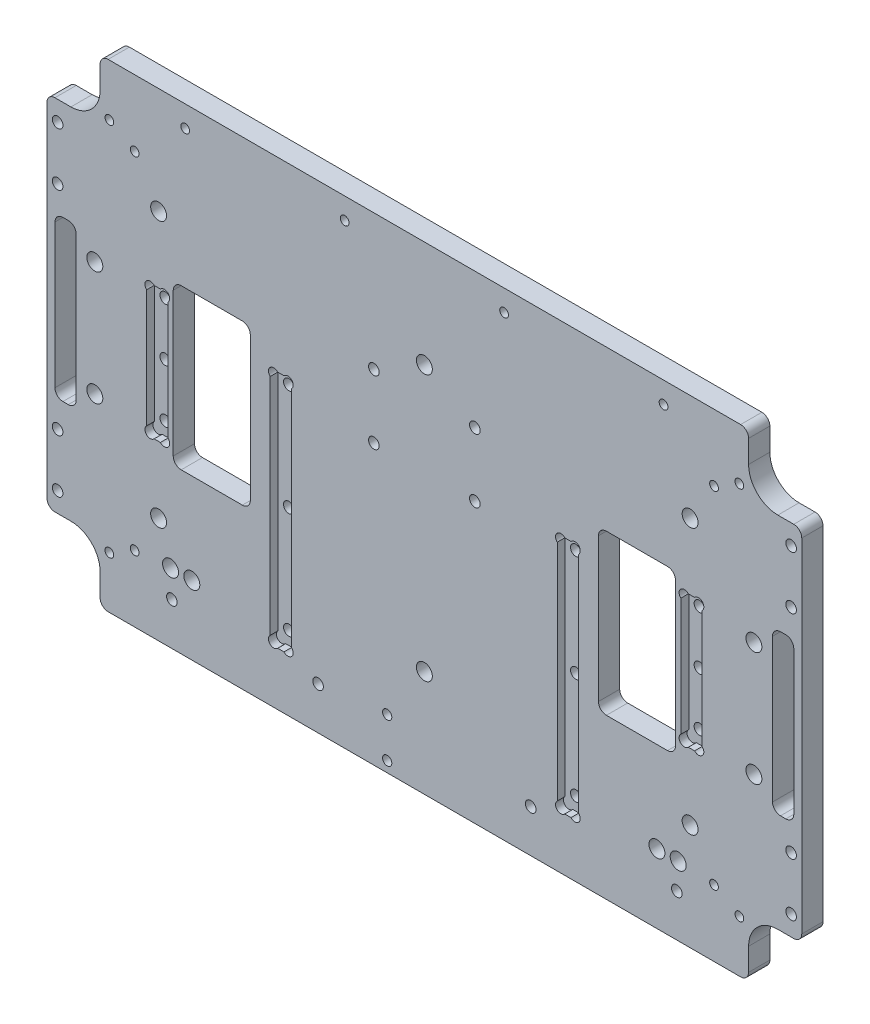
SolidWorks part; units mm, degrees
ref_plane "Front" through (0, 0, 0) normal (0, 0, 1) x (1, 0, 0)
ref_plane "Top" through (0, 0, 0) normal (0, 1, 0) x (1, 0, 0)
ref_plane "Right" through (0, 0, 0) normal (1, 0, 0) x (0, 0, -1)
sketch "Esquisse1" plane through (0, 0, 0) normal (0, 0, 1) x (1, 0, 0)
  line L1 (0, 0) -> (284, 0)
  line L2 (0, 0) -> (0, 180)
  line L3 (0, 180) -> (284, 180)
  line L4 (284, 0) -> (284, 180)
  dimension "D1" = 284
  dimension "D2" = 180
extrude "Boss.-Extru.1" add sketch "Esquisse1" along normal blind 8
sketch "Esquisse2" plane through (0, 0, 8) normal (0, 0, 1) x (1, 0, 0)
  line L0 (142, 180) -> (142, 0) construction
  line L1 (47.5, 60) -> (76.5, 60)
  line L2 (47.5, 60) -> (47.5, 120)
  line L3 (47.5, 120) -> (76.5, 120)
  line L4 (76.5, 60) -> (76.5, 120)
  line L5 (284, 180) -> (0, 180) construction
  line L6 (0, 0) -> (284, 0) construction
  line L7 (76.5, 90) -> (142, 90) construction
  line L8 (62, 60) -> (62, 120) construction
  line L9 (47.5, 90) -> (11, 90) construction
  line L10 (7, 60) -> (7, 120) construction
  line L11 (3, 60) -> (11, 60)
  line L12 (3, 60) -> (3, 120)
  line L13 (3, 120) -> (11, 120)
  line L14 (11, 60) -> (11, 120)
  line L15 (277, 60) -> (277, 120) construction
  line L16 (236.5, 90) -> (273, 90) construction
  line L17 (222, 60) -> (222, 120) construction
  line L18 (273, 60) -> (273, 120)
  line L19 (281, 120) -> (273, 120)
  line L20 (281, 60) -> (281, 120)
  line L21 (281, 60) -> (273, 60)
  line L22 (207.5, 60) -> (207.5, 120)
  line L23 (236.5, 120) -> (207.5, 120)
  line L24 (236.5, 60) -> (236.5, 120)
  line L25 (236.5, 60) -> (207.5, 60)
  dimension "D1" = 90
  dimension "D2" = 60
  dimension "D3" = 29
  dimension "D4" = 160
  dimension "D5" = 8
  dimension "D6" = 60
  dimension "D7" = 270
extrude "Enlèv. mat.-Extru.1" cut sketch "Esquisse2" against normal through all
sketch "Esquisse3" plane through (0, 0, 8) normal (0, 0, 1) x (1, 0, 0)
  line L0 (0, 172) -> (284, 172) construction
  line L1 (0, 180) -> (0, 0) construction
  line L2 (284, 0) -> (284, 180) construction
  line L3 (112, 172) -> (112, 180.3897) construction
  line L5 (172, 172) -> (172, 180.3897) construction
  line L6 (172, 180.3897) -> (112, 180.3897) construction
  line L7 (142, 180.3897) -> (142, 180) construction
  line L8 (284, 180) -> (0, 180) construction
  circle A0 centre (112, 172) radius 1.65
  circle A1 centre (172, 172) radius 1.65
  circle A2 centre (232, 172) radius 1.65
  circle A4 centre (52, 172) radius 1.65
  dimension "D1" = 3.3
  dimension "D2" = 4
  dimension "D3" = 8
  dimension "D4" = 60
extrude "Enlèv. mat.-Extru.2" cut sketch "Esquisse3" against normal up to vertex (8 mm away) up to point (284, 180, 0)
sketch "Esquisse4" plane through (0, 0, 8) normal (0, 0, 1) x (1, 0, 0)
  line L0 (142, 0) -> (142, 180) construction
  line L1 (84, 110) -> (92, 110)
  line L2 (84, 110) -> (84, 20)
  line L3 (84, 20) -> (92, 20)
  line L4 (92, 110) -> (92, 20)
  line L5 (0, 0) -> (284, 0) construction
  line L6 (284, 180) -> (0, 180) construction
  line L8 (76.5, 60) -> (76.5, 120) construction
  line L9 (192, 110) -> (192, 20)
  line L10 (200, 20) -> (192, 20)
  line L11 (200, 110) -> (200, 20)
  line L12 (200, 110) -> (192, 110)
  line L13 (47.5, 120) -> (47.5, 60) construction
  line L14 (37.5, 115) -> (45.5, 115)
  line L15 (37.5, 115) -> (37.5, 65)
  line L16 (37.5, 65) -> (45.5, 65)
  line L17 (45.5, 115) -> (45.5, 65)
  line L18 (45.5, 90) -> (47.5, 90) construction
  line L19 (238.5, 90) -> (236.5, 90) construction
  line L20 (238.5, 115) -> (238.5, 65)
  line L21 (246.5, 65) -> (238.5, 65)
  line L22 (246.5, 115) -> (246.5, 65)
  line L23 (246.5, 115) -> (238.5, 115)
  line L24 (47.5, 60) -> (76.5, 60) construction
  dimension "D1" = 40
  dimension "D2" = 90
  dimension "D3" = 8
  dimension "D4" = 7.5
  dimension "D5" = 8
  dimension "D6" = 2
  dimension "D7" = 50
extrude "Enlèv. mat.-Extru.3" cut sketch "Esquisse4" against normal blind 3
sketch "Esquisse5" plane through (0, 0, 8) normal (0, 0, 1) x (1, 0, 0)
  line L0 (142, 0) -> (142, 124.0722) construction
  line L2 (142, 117) -> (121.1311, 117) construction
  line L3 (0, 180) -> (0, 0) construction
  circle A0 centre (123, 129) radius 2
  circle A1 centre (123, 105) radius 2
  circle A2 centre (161, 105) radius 2
  circle A3 centre (161, 129) radius 2
  circle A5 centre (112, 172) radius 1.65 construction
  dimension "D1" = 38
  dimension "D2" = 4
  dimension "D3" = 24
  dimension "D4" = 55
  dimension "D5" = 142
extrude "Enlèv. mat.-Extru.4" cut sketch "Esquisse5" against normal through all
sketch "Esquisse6" plane through (0, 0, 8) normal (0, 0, 1) x (1, 0, 0)
  line L0 (142, 0) -> (142, 119.0936) construction
  line L1 (0, 0) -> (284, 0) construction
  line L2 (11, 90) -> (29.8915, 90) construction
  line L4 (11, 60) -> (11, 120) construction
  line L5 (273, 90) -> (254.1085, 90) construction
  circle A0 centre (18, 111.5) radius 3
  circle A1 centre (18, 68.5) radius 3
  circle A2 centre (266, 68.5) radius 3
  circle A3 centre (266, 111.5) radius 3
  dimension "D3" = 6
  dimension "D1" = 21.5
  dimension "D2" = 7
extrude "Enlèv. mat.-Extru.5" cut sketch "Esquisse6" against normal through all
sketch "Esquisse8" plane through (0, 0, 8) normal (0, 0, 1) x (1, 0, 0)
  line L0 (142, 180) -> (142, 109.7669) construction
  line L1 (0, 180) -> (20, 180)
  line L2 (0, 180) -> (0, 157.5)
  line L3 (0, 157.5) -> (20, 157.5)
  line L4 (20, 180) -> (20, 157.5)
  line L5 (284, 180) -> (0, 180) construction
  line L6 (264, 180) -> (264, 157.5)
  line L7 (284, 157.5) -> (264, 157.5)
  line L8 (284, 180) -> (284, 157.5)
  line L9 (284, 180) -> (264, 180)
  line L10 (264, 0) -> (264, 22.5)
  line L11 (0, 0) -> (20, 0)
  line L12 (0, 0) -> (0, 22.5)
  line L13 (0, 22.5) -> (20, 22.5)
  line L14 (20, 0) -> (20, 22.5)
  line L15 (284, 22.5) -> (264, 22.5)
  line L16 (284, 0) -> (284, 22.5)
  line L17 (284, 0) -> (264, 0)
  dimension "D1" = 22.5
  dimension "D2" = 20
  dimension "D3" = 22.5
extrude "Enlèv. mat.-Extru.7" cut sketch "Esquisse8" against normal through all
fillet "Congé1" radius 11 4 edges at (20, 157.5, 4) (264, 157.5, 4) (264, 22.5, 4) (20, 22.5, 4)
sketch "Esquisse7" plane through (0, 0, 8) normal (0, 0, 1) x (1, 0, 0)
  line L0 (142, 180) -> (142, 7.3256) construction
  line L1 (264, 180) -> (20, 180) construction
  line L2 (23.4737, 160.5) -> (33, 155) construction
  line L3 (264, 180) -> (20, 180) construction
  line L4 (260.5263, 160.5) -> (251, 155) construction
  line L5 (33, 155) -> (33, 25) construction
  line L6 (33, 90) -> (100.6533, 90) construction
  line L7 (23.4737, 19.5) -> (33, 25) construction
  line L8 (20, 0) -> (264, 0) construction
  line L9 (260.5263, 19.5) -> (251, 25) construction
  circle A0 centre (33, 155) radius 1.65
  circle A1 centre (23.4737, 160.5) radius 1.65
  circle A2 centre (260.5263, 160.5) radius 1.65
  circle A3 centre (251, 155) radius 1.65
  circle A5 centre (23.4737, 19.5) radius 1.65
  circle A6 centre (33, 25) radius 1.65
  circle A7 centre (251, 25) radius 1.65
  circle A8 centre (260.5263, 19.5) radius 1.65
  dimension "D1" = 3.3
  dimension "D5" = 25
  dimension "D2" = 11
  dimension "D3" = 109
  dimension "D4" = 30
  dimension "D6" = 25
extrude "Enlèv. mat.-Extru.6" cut sketch "Esquisse7" against normal through all
fillet "Congé2" radius 3 16 edges at (281, 60, 4) (273, 60, 4) (281, 120, 4) (273, 120, 4) (236.5, 120, 4) (207.5, 120, 4) (236.5, 60, 4) (207.5, 60, 4) (76.5, 60, 4) (47.5, 60, 4) (76.5, 120, 4) (47.5, 120, 4) (11, 120, 4) (3, 120, 4) (3, 60, 4) (11, 60, 4)
sketch "Esquisse9" plane through (0, 0, 8) normal (0, 0, 1) x (1, 0, 0)
  line L0 (37.5, 115) -> (38.8435, 113.6565) construction
  line L1 (45.5, 115) -> (37.5, 115) construction
  line L2 (41.5, 115) -> (41.5, 118.2808) construction
  line L3 (45.5, 115) -> (37.5, 115) construction
  line L4 (45.5, 115) -> (44.1565, 113.6565) construction
  line L5 (45.5, 90) -> (42.8729, 90) construction
  line L6 (45.5, 65) -> (45.5, 115) construction
  line L7 (45.5, 65) -> (44.1565, 66.3435) construction
  line L8 (37.5, 65) -> (38.8435, 66.3435) construction
  line L9 (45.5, 90) -> (238.5, 90) construction
  line L10 (238.5, 115) -> (238.5, 65) construction
  line L11 (142, 90) -> (142, 121.5895) construction
  line L12 (246.5, 65) -> (245.1565, 66.3435) construction
  line L13 (238.5, 65) -> (239.8435, 66.3435) construction
  line L14 (238.5, 90) -> (241.1271, 90) construction
  line L15 (238.5, 115) -> (239.8435, 113.6565) construction
  line L16 (242.5, 115) -> (242.5, 118.2808) construction
  line L17 (246.5, 115) -> (245.1565, 113.6565) construction
  line L18 (84, 110) -> (85.3435, 108.6565) construction
  line L19 (92, 110) -> (84, 110) construction
  line L20 (88, 110) -> (88, 112.2434) construction
  line L21 (92, 110) -> (84, 110) construction
  line L22 (92, 110) -> (90.6565, 108.6565) construction
  line L23 (84, 65) -> (89.3356, 65) construction
  line L24 (84, 110) -> (84, 20) construction
  line L25 (92, 20) -> (90.6565, 21.3435) construction
  line L26 (88, 20) -> (88, 17.7566) construction
  line L27 (84, 20) -> (85.3435, 21.3435) construction
  line L28 (200, 20) -> (198.6565, 21.3435) construction
  line L29 (196, 20) -> (196, 17.7566) construction
  line L30 (192, 20) -> (193.3435, 21.3435) construction
  line L31 (200, 65) -> (194.6644, 65) construction
  line L32 (192, 110) -> (193.3435, 108.6565) construction
  line L33 (196, 110) -> (196, 112.2434) construction
  line L34 (200, 110) -> (198.6565, 108.6565) construction
  circle A0 centre (38.8435, 113.6565) radius 2
  circle A1 centre (44.1565, 113.6565) radius 2
  circle A2 centre (44.1565, 66.3435) radius 2
  circle A3 centre (38.8435, 66.3435) radius 2
  circle A4 centre (245.1565, 66.3435) radius 2
  circle A5 centre (239.8435, 66.3435) radius 2
  circle A6 centre (239.8435, 113.6565) radius 2
  circle A7 centre (245.1565, 113.6565) radius 2
  circle A8 centre (85.3435, 108.6565) radius 2
  circle A9 centre (90.6565, 108.6565) radius 2
  circle A10 centre (90.6565, 21.3435) radius 2
  circle A11 centre (85.3435, 21.3435) radius 2
  circle A12 centre (198.6565, 21.3435) radius 2
  circle A13 centre (193.3435, 21.3435) radius 2
  circle A14 centre (193.3435, 108.6565) radius 2
  circle A15 centre (198.6565, 108.6565) radius 2
  dimension "D1" = 4
  dimension "D6" = 4
  dimension "D2" = 45
  dimension "D3" = 1.9
  dimension "D4" = 45
  dimension "D5" = 1.9
extrude "Enlèv. mat.-Extru.8" cut sketch "Esquisse9" against normal up to vertex (3 mm away) up to point (37.5, 65, 5)
fillet "Congé3" radius 3 8 edges at (264, 180, 4) (284, 157.5, 4) (284, 22.5, 4) (264, 0, 4) (20, 0, 4) (0, 22.5, 4) (0, 157.5, 4) (20, 180, 4)
sketch "Esquisse10" plane through (0, 0, 5) normal (0, 0, 1) x (1, 0, 0)
  line L0 (41.5, 115) -> (41.5, 65) construction
  line L1 (42.6749, 115) -> (40.3251, 115) construction
  line L2 (40.3251, 65) -> (42.6749, 65) construction
  line L3 (41.5, 90) -> (37.5, 90) construction
  line L4 (37.5, 112.1749) -> (37.5, 67.8251) construction
  line L5 (88, 110) -> (88, 20) construction
  line L6 (89.1749, 110) -> (86.8251, 110) construction
  line L7 (86.8251, 20) -> (89.1749, 20) construction
  line L8 (88, 65) -> (84, 65) construction
  line L9 (84, 107.1749) -> (84, 22.8251) construction
  line L10 (142, 0) -> (142, 180) construction
  line L11 (23, 0) -> (261, 0) construction
  line L12 (261, 180) -> (23, 180) construction
  line L13 (196, 65) -> (200, 65) construction
  line L14 (196, 110) -> (196, 20) construction
  line L15 (242.5, 90) -> (246.5, 90) construction
  line L16 (242.5, 115) -> (242.5, 65) construction
  circle A0 centre (41.5, 90) radius 2
  circle A1 centre (41.5, 70) radius 2
  circle A2 centre (41.5, 110) radius 2
  circle A3 centre (88, 65) radius 2
  circle A4 centre (88, 25) radius 2
  circle A5 centre (88, 105) radius 2
  circle A6 centre (196, 105) radius 2
  circle A7 centre (196, 25) radius 2
  circle A8 centre (196, 65) radius 2
  circle A9 centre (242.5, 110) radius 2
  circle A10 centre (242.5, 70) radius 2
  circle A11 centre (242.5, 90) radius 2
  dimension "D1" = 4
  dimension "D2" = 20
  dimension "D3" = 40
extrude "Enlèv. mat.-Extru.9" cut sketch "Esquisse10" against normal through all
sketch "Esquisse11" plane through (0, 0, 8) normal (0, 0, 1) x (1, 0, 0)
  line L0 (142, 0) -> (142, 52.4414) construction
  line L1 (23, 0) -> (261, 0) construction
  line L2 (142, 16) -> (47, 16) construction
  line L3 (86.8251, 20) -> (89.1749, 20) construction
  line L4 (46.5, 26) -> (54.5, 26) construction
  line L5 (237.5, 26) -> (229.5, 26) construction
  circle A0 centre (47, 16) radius 2
  circle A1 centre (237, 16) radius 2
  circle A2 centre (102, 16) radius 2
  circle A3 centre (46.5, 26) radius 3
  circle A4 centre (54.5, 26) radius 3
  circle A5 centre (229.5, 26) radius 3
  circle A6 centre (237.5, 26) radius 3
  circle A7 centre (182, 16) radius 2
  point P10 (94.5, 16)
  point P13 (88, 20)
  dimension "D1" = 4
  dimension "D2" = 190
  dimension "D4" = 8
  dimension "D5" = 10
  dimension "D7" = 6
  dimension "D8" = 80
  dimension "D3" = 4
  dimension "D6" = 87.5
extrude "Enlèv. mat.-Extru.10" cut sketch "Esquisse11" against normal through all
sketch "Esquisse12" plane through (0, 0, 8) normal (0, 0, 1) x (1, 0, 0)
  line L0 (128, 0) -> (128, 19) construction
  line L1 (23, 0) -> (261, 0) construction
  circle A0 centre (128, 4) radius 1.75
  circle A1 centre (128, 19) radius 1.75
  dimension "D1" = 15
  dimension "D2" = 3.5
  dimension "D3" = 4
  dimension "D4" = 128
extrude "Enlèv. mat.-Extru.11" cut sketch "Esquisse12" against normal through all
sketch "Esquisse13" plane through (0, 0, 8) normal (0, 0, 1) x (1, 0, 0)
  line L0 (4, 157.5) -> (4, 22.5) construction
  line L1 (3, 157.5) -> (9, 157.5) construction
  line L2 (9, 22.5) -> (3, 22.5) construction
  line L3 (0, 154.5) -> (0, 25.5) construction
  line L4 (11, 90) -> (4, 90) construction
  line L5 (11, 63) -> (11, 117) construction
  line L6 (142, 0) -> (142, 180) construction
  line L7 (23, 0) -> (261, 0) construction
  line L8 (261, 180) -> (23, 180) construction
  line L9 (273, 90) -> (280, 90) construction
  line L10 (280, 157.5) -> (280, 22.5) construction
  circle A0 centre (4, 30) radius 2
  circle A1 centre (4, 50) radius 2
  circle A2 centre (4, 130) radius 2
  circle A3 centre (4, 150) radius 2
  circle A4 centre (280, 150) radius 2
  circle A5 centre (280, 130) radius 2
  circle A6 centre (280, 50) radius 2
  circle A7 centre (280, 30) radius 2
  dimension "D2" = 20
  dimension "D3" = 4
  dimension "D4" = 80
  dimension "D1" = 4
extrude "Enlèv. mat.-Extru.12" cut sketch "Esquisse13" against normal through all
sketch "Esquisse14" plane through (0, 0, 8) normal (0, 0, 1) x (1, 0, 0)
  line L0 (142, 0) -> (142, 180) construction
  line L1 (23, 0) -> (261, 0) construction
  line L2 (261, 180) -> (23, 180) construction
  line L3 (142, 90) -> (0, 90) construction
  line L4 (0, 154.5) -> (0, 25.5) construction
  line L5 (142, 40) -> (42, 40) construction
  circle A0 centre (42, 140) radius 3
  circle A1 centre (42, 40) radius 3
  circle A2 centre (242, 40) radius 3
  circle A3 centre (242, 140) radius 3
  circle A4 centre (142, 40) radius 3
  circle A5 centre (142, 140) radius 3
  dimension "D3" = 6
  dimension "D1" = 200
  dimension "D2" = 50
extrude "fixations_usinage" cut sketch "Esquisse14" against normal through all both and the other way through all
